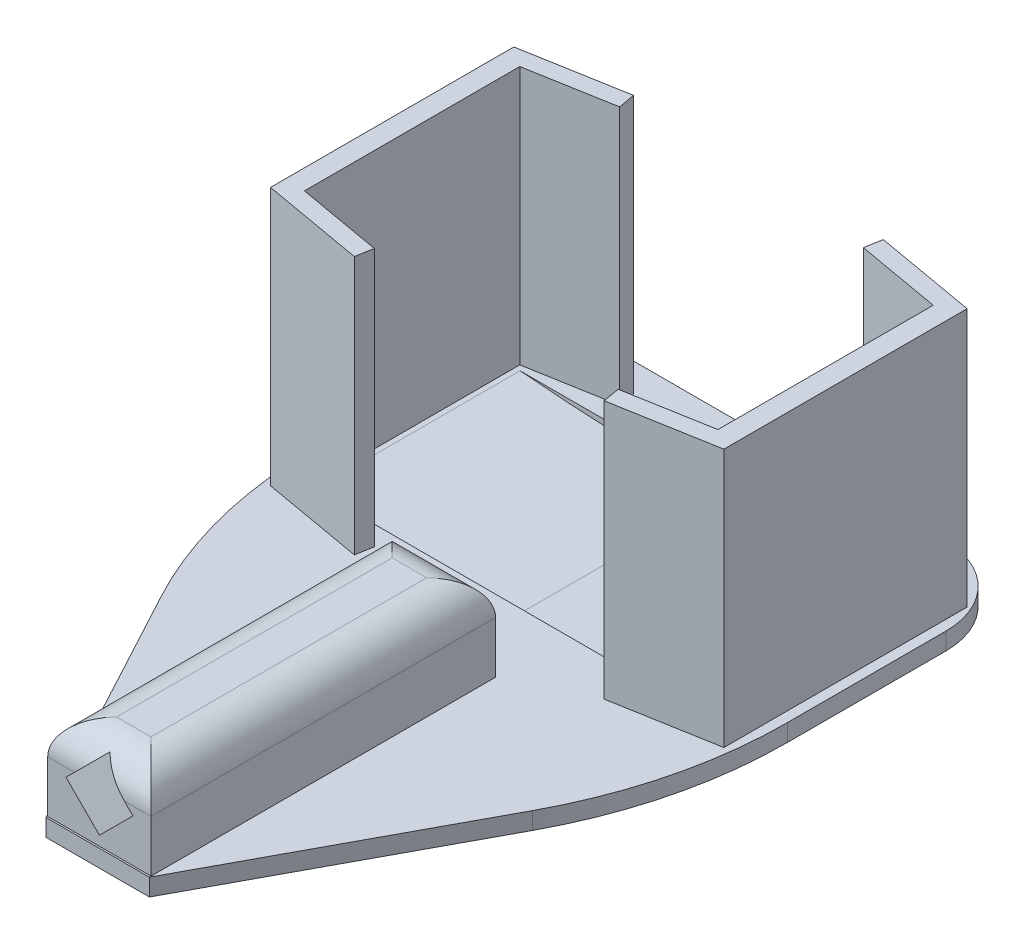
SolidWorks part; units mm, degrees
ref_plane "Front Plane" through (0, 0, 0) normal (0, 0, 1) x (1, 0, 0)
ref_plane "Top Plane" through (0, 0, 0) normal (0, 1, 0) x (1, 0, 0)
ref_plane "Right Plane" through (0, 0, 0) normal (1, 0, 0) x (0, 0, -1)
sketch "Sketch1" plane through (0, 0, 0) normal (0, 1, 0) x (1, 0, 0)
  line L0 (-6, -38.9038) -> (6, -38.9038)
  line L1 (-27.5, -38.9038) -> (27.5, -38.9038)
  line L2 (-27.5, -38.9038) -> (-27.5, 41.0962)
  line L3 (-27.5, 41.0962) -> (27.5, 41.0962)
  line L4 (27.5, -38.9038) -> (27.5, 41.0962)
  line L5 (6, -38.9038) -> (27.5, 1.0962)
  line L6 (-6, -38.9038) -> (-27.5, 1.0962)
  point P0 (0, 21.0962)
  point P7 (0, -38.9038)
  dimension "D1" = 55
  dimension "D2" = 80
  dimension "D3" = 12
extrude "Boss-Extrude1" add sketch "Sketch1" along normal blind 2 contours L6 L0 L5 L4 L3 L2 region at (0, 0, -7.5746)
sketch "Sketch2" plane through (0, 2, 0) normal (0, 1, 0) x (1, 0, 0)
  line L0 (0, 21.6017) -> (0, 34.1017)
  line L1 (-24, 21.6017) -> (24, 21.6017)
  line L2 (24, 9.1017) -> (24, 34.1017)
  line L3 (24, 34.1017) -> (14.1519, 35.8381)
  line L4 (14.1519, 35.8381) -> (14.4992, 37.8078)
  line L5 (14.4992, 37.8078) -> (26.3169, 35.724)
  line L6 (26.3169, 35.724) -> (26.3169, 7.4793)
  line L7 (24, 9.1017) -> (14.1519, 7.3652)
  line L8 (14.1519, 7.3652) -> (14.4992, 5.3956)
  line L9 (14.4992, 5.3956) -> (26.3169, 7.4793)
  line L10 (-14.1519, 7.3652) -> (-14.4992, 5.3956)
  line L11 (-14.4992, 5.3956) -> (-26.3169, 7.4793)
  line L12 (-24, 9.1017) -> (-14.1519, 7.3652)
  line L13 (-26.3169, 35.724) -> (-26.3169, 7.4793)
  line L14 (-24, 9.1017) -> (-24, 34.1017)
  line L15 (-14.4992, 37.8078) -> (-26.3169, 35.724)
  line L16 (-14.1519, 35.8381) -> (-14.4992, 37.8078)
  line L17 (-24, 34.1017) -> (-14.1519, 35.8381)
  point P5 (0, 34.1017)
  point P6 (0, 21.6017)
  point P9 (24, 21.6017)
  point P16 (26.3169, 21.6017)
  dimension "D1" = 12.5
  dimension "D2" = 48
  dimension "D3" = 10
  dimension "D4" = 90
  dimension "D5" = 2
  dimension "D6" = 12
extrude "Boss-Extrude2" add sketch "Sketch2" along normal blind 30 contours L14 L17 L16 L15 L13 L11 L10 L12 | L8 L9 L6 L5 L4 L3 L2 L7 region at (24.3462, 2, -27.8517) region at (-24.3462, 2, -15.3517)
sketch "Sketch3" plane through (0, 2, 0) normal (0, 1, 0) x (1, 0, 0)
  line L1 (-6.0055, -38.7) -> (5.9945, -38.7)
  line L2 (-6.0055, -38.7) -> (-6.0055, 1.3)
  line L3 (-6.0055, 1.3) -> (5.9945, 1.3)
  line L4 (5.9945, -38.7) -> (5.9945, 1.3)
  line L5 (-6.0055, -38.7) -> (5.9945, 1.3) construction
  line L6 (-6.0055, 1.3) -> (5.9945, -38.7) construction
  point P0 (-0.0055, -18.7)
  dimension "D1" = 40
  dimension "D2" = 12
  dimension "D3" = 18.7
extrude "Boss-Extrude3" add sketch "Sketch3" along normal blind 10
sketch "Sketch4" plane through (0, 0, 38.7) normal (0, 0, 1) x (1, 0, 0)
  line L0 (0, 0) -> (0, 7)
  line L2 (0, 3.1109) -> (3.8891, 7)
  line L3 (0, 3.1109) -> (-3.8891, 7)
  line L4 (-3.8891, 7) -> (0, 10.8891)
  line L5 (3.8891, 7) -> (0, 10.8891)
  line L6 (0, 3.1109) -> (0, 10.8891) construction
  line L7 (-3.8891, 7) -> (3.8891, 7) construction
  dimension "D1" = 5.5
  dimension "D2" = 5.5
  dimension "D3" = 7
extrude "Cut-Extrude1" cut sketch "Sketch4" against normal blind 35 contours L2 L5 L4 L3 region at (-1.8668, 5.1332, 38.7)
sketch "Sketch6" plane through (0, 2, 0) normal (0, 1, 0) x (1, 0, 0)
  line L1 (-23.3983, 33.5266) -> (23.3983, 33.5266)
  line L2 (-23.3983, 33.5266) -> (-23.3983, 9.6446)
  line L3 (-23.3983, 9.6446) -> (23.3983, 9.6446)
  line L4 (23.3983, 33.5266) -> (23.3983, 9.6446)
  line L5 (-23.3983, 33.5266) -> (23.3983, 9.6446) construction
  line L6 (-23.3983, 9.6446) -> (23.3983, 33.5266) construction
  point P0 (0, 21.5856)
extrude "Cut-Extrude2" cut sketch "Sketch6" against normal blind 1
fillet "Fillet1" radius 280 2 edges at (23.3983, 1, -21.5856) (-23.3983, 1, -21.5856)
fillet "Fillet2" radius 9 2 edges at (27.5, 1, -41.0962) (-27.5, 1, -41.0962)
fillet "Fillet3" radius 4 4 edges at (-0.0055, 12, -1.3) (-6.0055, 12, 18.7) (5.9945, 12, 18.7) (-0.0055, 12, 38.7)
fillet "Fillet4" radius 50 2 edges at (-27.5, 1, -1.0962) (27.5, 1, -1.0962)
